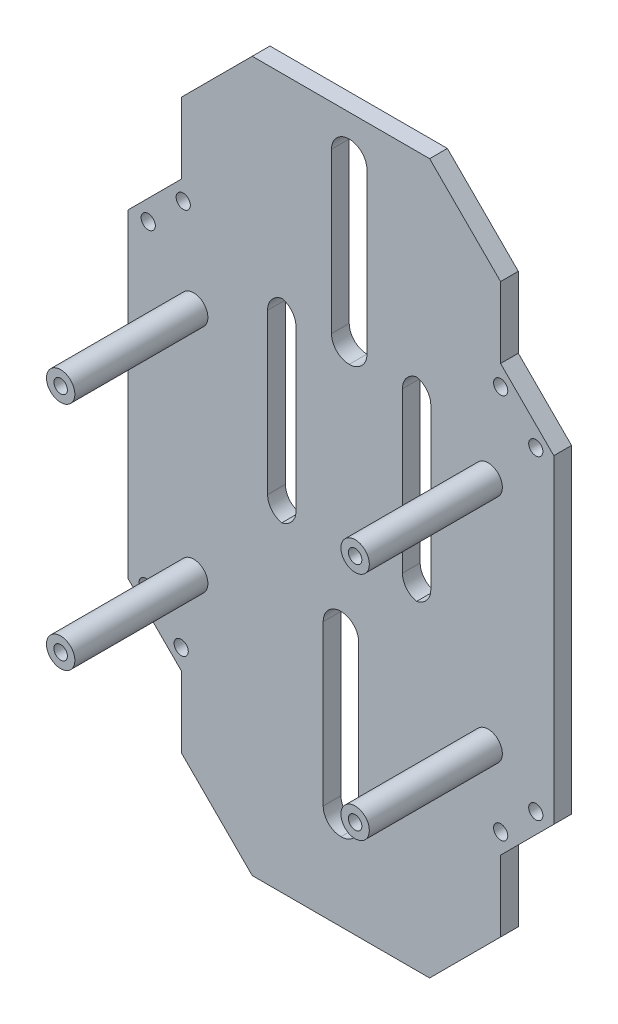
SolidWorks part; units mm, degrees
ref_plane "Plan de face" through (0, 0, 0) normal (0, 0, 1) x (1, 0, 0)
ref_plane "Plan de dessus" through (0, 0, 0) normal (0, 1, 0) x (1, 0, 0)
ref_plane "Plan de droite" through (0, 0, 0) normal (1, 0, 0) x (0, 0, -1)
sketch "Esquisse1" plane through (0, 0, 0) normal (0, 0, 1) x (1, 0, 0)
  line L0 (-41.0719, 30.2056) -> (78.9281, 30.2056)
  line L1 (78.9281, 30.2056) -> (78.9281, -89.7944)
  line L2 (78.9281, -89.7944) -> (-41.0719, -89.7944)
  line L3 (-41.0719, -89.7944) -> (-41.0719, 30.2056)
  dimension "D1" = 120
  dimension "D2" = 120
extrude "Boss.-Extru.2" add sketch "Esquisse1" along normal blind 5
sketch "Esquisse3" plane through (0, 0, 0) normal (0, 0, -1) x (-1, 0, 0)
sketch "Esquisse7" plane through (0, 0, 5) normal (0, 0, 1) x (1, 0, 0)
sketch "Esquisse9" plane through (0, 0, 5) normal (0, 0, 1) x (1, 0, 0)
  line L0 (-41.0719, -89.7944) -> (78.9281, -89.7944) construction
  line L1 (78.9281, -89.7944) -> (78.9281, 30.2056) construction
  circle A0 centre (-22.5719, -64.7944) radius 4
  circle A1 centre (-22.5719, 0.2056) radius 4
  circle A2 centre (60.4281, 0.2056) radius 4
  circle A3 centre (60.4281, -64.7944) radius 4
  point P8 (0, 0)
  point P13 (0, 0)
  point P14 (63.712, -64.7944)
  dimension "D5" = 8
  dimension "D6" = 8
  dimension "D7" = 8
  dimension "D8" = 8
  dimension "D1" = 83
  dimension "D2" = 83
  dimension "D3" = 18.5
  dimension "D4" = 65
  dimension "D9" = 25
  dimension "D10" = 25
  dimension "D11" = 18.5
extrude "Boss.-Extru.4" add sketch "Esquisse9" along normal blind 37.5
chamfer "Chanfrein5" distance 15 angle 45 1 edges at (78.9281, -89.7944, 2.5)
chamfer "Chanfrein6" distance 15 angle 45 1 edges at (78.9281, 30.2056, 2.5)
chamfer "Chanfrein7" distance 15 angle 45 1 edges at (-41.0719, 30.2056, 2.5)
chamfer "Chanfrein8" distance 15 angle 45 1 edges at (-41.0719, -89.7944, 2.5)
hole_wizard "Dégagement #61" positions "Esquisse3D4" profile "Esquisse18" hole size "#6" standard "Ansi Pouces"
sketch3d "Esquisse3D4"
  line L0 (-22.5719, -64.7944, 42.5) -> (-22.5719, -64.7944, 5) construction
  line L1 (60.4281, -64.7944, 42.5) -> (60.4281, -64.7944, 5) construction
  line L2 (60.4281, 0.2056, 42.5) -> (60.4281, 0.2056, 5) construction
  line L3 (-22.5719, 0.2056, 42.5) -> (-22.5719, 0.2056, 5) construction
  point P0 (-22.5719, -64.7944, 42.5)
  point P4 (60.4281, -64.7944, 42.5)
  point P8 (60.4281, 0.2056, 42.5)
  point P12 (-22.5719, 0.2056, 42.5)
sketch "Esquisse18" plane through (-22.5719, -64.7944, 42.5) normal (1, 0, 0) x (0, -1, 0)
  line L0 (0, 0) -> (0, 11.1408)
  line L1 (0, 11.1408) -> (1.8986, 10)
  line L2 (1.8986, 10) -> (1.8986, 0)
  line L5 (1.8986, 0) -> (0, 0)
  line L10 (0, 11.1408) -> (-1.8986, 10) construction
  line L11 (0, -6.35) -> (0, 107.95) construction
  dimension "Diamètre du perçage" = 3.7973
  dimension "Profondeur du perçage" = 10
  dimension "Angle de pointe" = 118
cosmetic thread "Représentation de filetage1"
sketch "Esquisse21" plane through (0, -89.7944, 0) normal (0, -1, 0) x (-1, 0, 0)
  line L0 (26.0719, -5) -> (26.0719, 0)
  line L1 (26.0719, 0) -> (-63.9281, 0)
  line L2 (-63.9281, 0) -> (-63.9281, -5)
  line L3 (-63.9281, -5) -> (26.0719, -5)
extrude "Boss.-Extru.7" add sketch "Esquisse21" along normal blind 40
sketch "Esquisse22" plane through (0, 30.2056, 0) normal (0, 1, 0) x (1, 0, 0)
  line L0 (63.9281, -5) -> (63.9281, 0)
  line L1 (63.9281, 0) -> (-26.0719, 0) construction
  line L2 (63.9281, 0) -> (-26.0719, 0)
  line L3 (-26.0719, 0) -> (-26.0719, -5)
  line L4 (-26.0719, -5) -> (63.9281, -5)
extrude "Boss.-Extru.8" add sketch "Esquisse22" along normal blind 40
chamfer "Chanfrein23" distance 20 angle 45 4 edges at (-26.0719, -129.7944, 2.5) (63.9281, -129.7944, 2.5) (-26.0719, 70.2056, 2.5) (63.9281, 70.2056, 2.5)
sketch "Esquisse23" plane through (0, 0, 5) normal (0, 0, 1) x (1, 0, 0)
  line L0 (-41.0719, -74.7944) -> (-26.0719, -89.7944) construction
  line L1 (-26.0719, 30.2056) -> (-41.0719, 15.2056) construction
  line L3 (78.9281, 15.2056) -> (63.9281, 30.2056) construction
  line L5 (63.9281, -89.7944) -> (78.9281, -74.7944) construction
  circle A0 centre (-35.9963, -74.2132) radius 2
  circle A1 centre (-26.0968, -84.1127) radius 2
  circle A2 centre (-25.5241, 25.0966) radius 2
  circle A3 centre (-35.3901, 15.1637) radius 2
  circle A4 centre (63.9532, 24.5237) radius 2
  circle A5 centre (73.8527, 14.6242) radius 2
  circle A6 centre (63.9532, -84.1124) radius 2
  circle A7 centre (73.8527, -74.2129) radius 2
  dimension "D3" = 4
  dimension "D4" = 4
  dimension "D6" = 4
  dimension "D7" = 4
  dimension "D10" = 5.6818
  dimension "D15" = 4
  dimension "D16" = 4
  dimension "D19" = 14
  dimension "D23" = 4
  dimension "D24" = 4
  dimension "D1" = 4
  dimension "D2" = 4
  dimension "D5" = 14
  dimension "D8" = 14
  dimension "D9" = 4
  dimension "D11" = 5.682
  dimension "D12" = 5.109
  dimension "D13" = 14
  dimension "D14" = 4
  dimension "D17" = 4
  dimension "D18" = 5.682
  dimension "D20" = 4
  dimension "D21" = 5.682
  dimension "D22" = 4
extrude "Enlèv. mat.-Extru.1" cut sketch "Esquisse23" against normal blind 10
sketch "Esquisse24" plane through (0, 0, 5) normal (0, 0, 1) x (1, 0, 0)
  line L0 (63.9281, -89.7944) -> (78.9281, -74.7944) construction
  circle A0 centre (63.5389, -84.5268) radius 2.5407
  circle A1 centre (73.4383, -74.6273) radius 2.5147
  dimension "D1" = 4
  dimension "D2" = 4
  dimension "D3" = 14
  dimension "D4" = 5.282
sketch "Sketch1" plane through (0, 0, 5) normal (0, 0, 1) x (1, 0, 0)
  line L1 (13.9281, -107.7944) -> (23.9281, -107.7944)
  line L2 (13.9281, -107.7944) -> (13.9281, -52.7944)
  line L3 (13.9281, -52.7944) -> (23.9281, -52.7944)
  line L4 (23.9281, -107.7944) -> (23.9281, -52.7944)
  line L6 (43.9281, -129.7944) -> (-6.0719, -129.7944) construction
  dimension "D1" = 10
  dimension "D2" = 55
  dimension "D3" = 40
  dimension "D4" = 22
extrude "Cut-Extrude2" cut sketch "Sketch1" against normal blind 5 contours L2 L1 L4 L3
fillet "Fillet2" radius 5 1 edges at (13.9281, -107.7944, 2.5)
fillet "Fillet3" radius 5 3 edges at (13.9281, -52.7944, 2.5) (23.9281, -52.7944, 2.5) (23.9281, -107.7944, 2.5)
sketch "Sketch2" plane through (0, 0, 5) normal (0, 0, 1) x (1, 0, 0)
  line L0 (23.9281, -102.7944) -> (23.9281, -57.7944) construction
  line L1 (41.9281, -96.2103) -> (33.9281, -96.2103)
  line L2 (41.9281, -96.2103) -> (41.9281, -41.2103)
  line L3 (41.9281, -41.2103) -> (33.9281, -41.2103)
  line L4 (33.9281, -96.2103) -> (33.9281, -41.2103)
  line L5 (13.9281, -102.7944) -> (13.9281, -57.7944) construction
  line L6 (3.9281, -96.2103) -> (-4.0719, -96.2103)
  line L7 (3.9281, -96.2103) -> (3.9281, -41.2103)
  line L8 (3.9281, -41.2103) -> (-4.0719, -41.2103)
  line L9 (-4.0719, -96.2103) -> (-4.0719, -41.2103)
  dimension "D1" = 10
  dimension "D2" = 10
  dimension "D3" = 8
  dimension "D4" = 8
  dimension "D5" = 55
  dimension "D6" = 55
sketch "Sketch3" plane through (0, 0, 5) normal (0, 0, 1) x (1, 0, 0)
  line L1 (26.2609, 63.6661) -> (16.2609, 63.6661)
  line L2 (26.2609, 63.6661) -> (26.2609, 8.6661)
  line L3 (26.2609, 8.6661) -> (16.2609, 8.6661)
  line L4 (16.2609, 63.6661) -> (16.2609, 8.6661)
  dimension "D1" = 10
  dimension "D2" = 55
  dimension "D3" = 40
extrude "Cut-Extrude4" cut sketch "Sketch3" against normal blind 5
fillet "Fillet11" radius 5 4 edges at (16.2609, 63.6661, 2.5) (26.2609, 63.6661, 2.5) (26.2609, 8.6661, 2.5) (16.2609, 8.6661, 2.5)
sketch "Sketch4" plane through (0, 0, 5) normal (0, 0, 1) x (1, 0, 0)
  line L0 (26.2609, 13.6661) -> (26.2609, 58.6661) construction
  line L1 (6.2609, 15.3765) -> (-1.7391, 15.3765)
  line L2 (6.2609, 15.3765) -> (6.2609, -39.6235)
  line L3 (6.2609, -39.6235) -> (-1.7391, -39.6235)
  line L4 (-1.7391, 15.3765) -> (-1.7391, -39.6235)
  line L5 (44.2609, 15.2056) -> (36.2609, 15.2056)
  line L6 (44.2609, 15.2056) -> (44.2609, -39.7944)
  line L7 (44.2609, -39.7944) -> (36.2609, -39.7944)
  line L8 (36.2609, 15.2056) -> (36.2609, -39.7944)
  line L9 (16.2609, 58.6661) -> (16.2609, 13.6661) construction
  dimension "D1" = 55
  dimension "D2" = 55
  dimension "D3" = 8
  dimension "D4" = 8
  dimension "D5" = 10
  dimension "D6" = 10
  dimension "D7" = 55
  dimension "D8" = 55
extrude "Cut-Extrude5" cut sketch "Sketch4" against normal blind 5
fillet "Fillet12" radius 5 4 edges at (44.2609, 15.2056, 2.5) (44.2609, -39.7944, 2.5) (36.2609, 15.2056, 2.5) (36.2609, -39.7944, 2.5)
sketch "Sketch12" plane through (-1.7391, 0, 0) normal (1, 0, 0) x (0, 0, -1)
extrude "Cut-Extrude6" cut sketch "Sketch4<2>" against normal blind 5
sketch "Sketch4<2>" plane through (0, 0, 5) normal (0, 0, 1) x (1, 0, 0) same geometry as "Sketch4"
fillet "Fillet16" radius 5 4 edges at (6.2609, -39.6235, 2.5) (6.2609, 15.3765, 2.5) (-1.7391, 15.3765, 2.5) (-1.7391, -39.6235, 2.5)
fillet "Fillet17" radius 5 4 edges at (36.2609, 15.2056, 2.5) (36.2609, -39.7944, 2.5) (44.2609, 15.2056, 2.5) (44.2609, -39.7944, 2.5)
